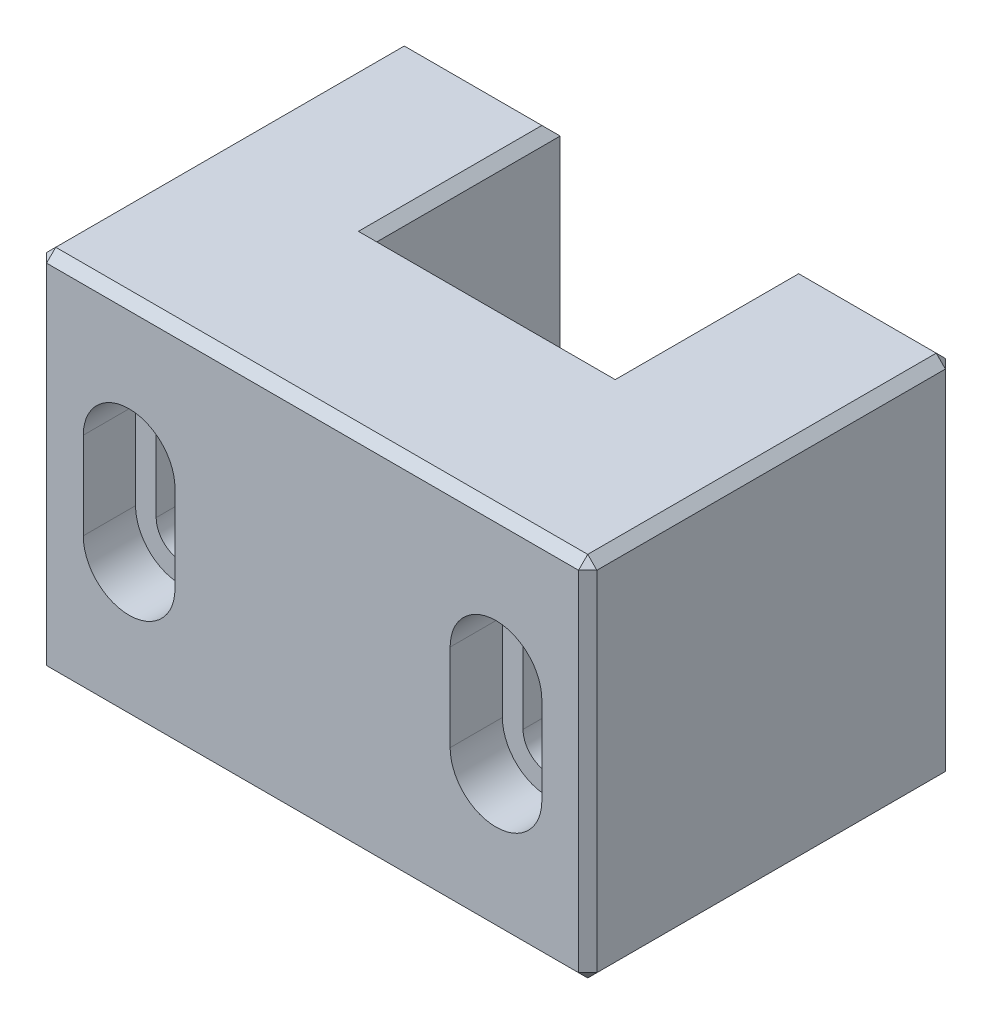
SolidWorks part; units mm, degrees
ref_plane "前视基准面" through (0, 0, 0) normal (0, 0, 1) x (1, 0, 0)
ref_plane "上视基准面" through (0, 0, 0) normal (0, 1, 0) x (1, 0, 0)
ref_plane "右视基准面" through (0, 0, 0) normal (1, 0, 0) x (0, 0, -1)
sketch "草图1" plane through (0, 0, 0) normal (0, 0, 1) x (1, 0, 0)
  line L1 (-30, 20) -> (30, 20)
  line L2 (-30, 20) -> (-30, -20)
  line L3 (-30, -20) -> (30, -20)
  line L4 (30, 20) -> (30, -20)
  line L5 (-30, 20) -> (30, -20) construction
  line L6 (-30, -20) -> (30, 20) construction
  point P0 (0, 0)
  dimension "D1" = 60
  dimension "D2" = 40
extrude "凸台-拉伸1" add sketch "草图1" along normal blind 40
sketch "草图6" plane through (0, 0, 40) normal (0, 0, 1) x (1, 0, 0)
  line L0 (-20, 0) -> (20, 0) construction
  point P4 (0, 0)
  dimension "D1" = 40
hole_wizard "打孔尺寸(%根据)内六角圆柱头螺钉的类型5" positions "草图7" profile "草图8" size "M5" standard "GB" slot yes end condition through all
sketch "草图7" plane through (0, 0, 40) normal (0, 0, 1) x (1, 0, 0)
  line L0 (-20, 7.5) -> (-20, -7.5) construction
  point P0 (-20, 0)
  point P3 (20, 0)
  dimension "D1" = 15
sketch "草图8" plane through (-20, 0, 40) normal (1, 0, 0) x (0, -1, 0)
  line L0 (0, 0) -> (0, 40)
  line L1 (0, 40) -> (2.75, 40)
  line L3 (2.75, 40) -> (2.75, 5.7)
  line L4 (2.75, 5.7) -> (5, 5.7)
  line L5 (5, 5.7) -> (5, 0)
  line L7 (5, 0) -> (0, 0)
  line L11 (0, -6.35) -> (0, 107.95) construction
  dimension "通孔孔直径" = 5.5
  dimension "通孔孔深度" = 40
  dimension "柱形沉头孔直径" = 10
  dimension "柱形沉头孔深度" = 5.7
sketch "草图9" plane through (0, -20, 0) normal (0, -1, 0) x (1, 0, 0)
  line L0 (0, 0) -> (0, 20) construction
  line L1 (-13, 20) -> (13, 20)
  line L2 (13, 20) -> (13, 0)
  line L3 (-30, 0) -> (30, 0) construction
  line L4 (13, 0) -> (-13, 0)
  line L5 (-13, 0) -> (-13, 20)
  point P6 (0, 20)
  dimension "D1" = 26
  dimension "D2" = 20
extrude "切除-拉伸1" cut sketch "草图9" against normal through all
chamfer "倒角1" distance 1 angle 45 20 edges at (-13, -20, 10) (-21.5, -20, 0) (0, -20, 40) (0, -20, 20) (13, -20, 10) (21.5, -20, 0) (0, 20, 40) (30, -20, 20) (30, 0, 40) (30, 20, 20) (30, 0, 0) (21.5, 20, 0) (13, 20, 10) (0, 20, 20) (-13, 20, 10) (-21.5, 20, 0) (-30, 20, 20) (-30, 0, 40) (-30, -20, 20) (-30, 0, 0)
